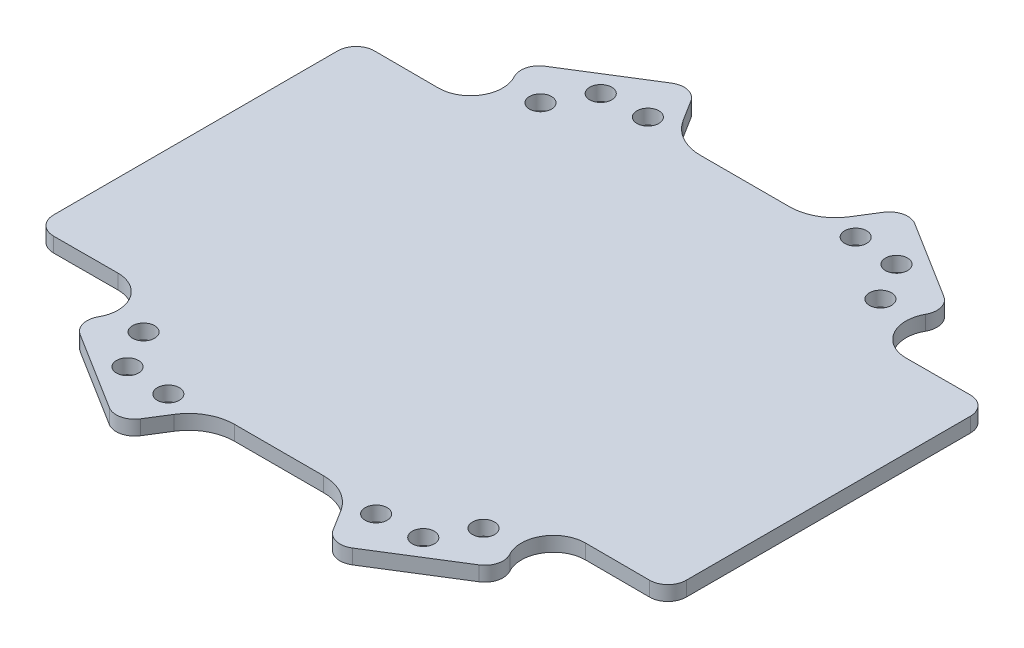
SolidWorks part; units mm, degrees
ref_plane "Front Plane" through (0, 0, 0) normal (0, 0, 1) x (1, 0, 0)
ref_plane "Top Plane" through (0, 0, 0) normal (0, 1, 0) x (1, 0, 0)
ref_plane "Right Plane" through (0, 0, 0) normal (1, 0, 0) x (0, 0, -1)
sketch "Sketch1" plane through (0, 0, 0) normal (0, 1, 0) x (1, 0, 0)
  line L0 (-17.5, 28) -> (-26.4999, 42.3999) construction
  line L1 (-28, 17.5) -> (28, 17.5) construction
  line L2 (-28, 17.5) -> (-28, -17.5) construction
  line L3 (-28, -17.5) -> (28, -17.5) construction
  line L4 (28, 17.5) -> (28, -17.5) construction
  line L5 (-28, 17.5) -> (28, -17.5) construction
  line L6 (-28, -17.5) -> (28, 17.5) construction
  line L7 (-17.5, 28) -> (17.5, 28) construction
  line L8 (-17.5, 28) -> (-17.5, -28) construction
  line L9 (-17.5, -28) -> (17.5, -28) construction
  line L10 (17.5, 28) -> (17.5, -28) construction
  line L11 (-17.5, 28) -> (17.5, -28) construction
  line L12 (-17.5, -28) -> (17.5, 28) construction
  line L13 (17.5, -28) -> (26.4999, -42.3999) construction
  line L14 (-23.436, 24.29) -> (-32.4359, 38.6899) construction
  line L15 (-23.436, 24.29) -> (11.564, -31.71) construction
  line L16 (11.564, -31.71) -> (20.564, -46.1099) construction
  line L17 (-11.564, 31.71) -> (-20.564, 46.1099) construction
  line L18 (-11.564, 31.71) -> (23.436, -24.29) construction
  line L19 (23.436, -24.29) -> (32.4359, -38.6899) construction
  line L20 (0, -28) -> (0, 28) construction
  line L21 (-34.5, 17.5) -> (-34.5, -17.5) construction
  line L22 (-34.5, 0) -> (34.5, 0) construction
  line L24 (34.5, 17.5) -> (34.5, -17.5) construction
  circle A0 centre (-26.4999, 42.3999) radius 25.4 construction
  circle A1 centre (-20, 9.5) radius 8 construction
  circle A2 centre (-26.4999, 42.3999) radius 8 construction
  point P4 (0, 0)
  point P11 (0, 0)
  dimension "D4" = 50.8
  dimension "D7" = 16
  dimension "D10" = 16
  dimension "D1" = 35
  dimension "D2" = 56
  dimension "D3" = 50
  dimension "D8" = 8
  dimension "D9" = 8
  dimension "D11" = 6.5
  dimension "D5" = 7
  dimension "D6" = 7
  dimension "D12" = 6.5
sketch "Sketch2" plane through (0, 0, 0) normal (0, 1, 0) x (1, 0, 0)
  line L0 (-34.5, -17.5) -> (-34.5, 17.5)
  line L1 (-34.5, 17.5) -> (-19.1649, 17.4563)
  line L2 (-23.436, 24.29) -> (11.564, -31.71) construction
  line L3 (-19.1649, 17.4563) -> (-23.436, 24.29)
  line L4 (-23.436, 24.29) -> (-11.564, 31.71)
  line L5 (-11.564, 31.71) -> (-7.6233, 25.4049)
  line L6 (-11.564, 31.71) -> (23.436, -24.29) construction
  line L7 (-7.6233, 25.4049) -> (7.6233, 25.4049)
  line L8 (0, -28) -> (0, 28) construction
  line L9 (0, -28) -> (0, 28) construction
  line L10 (-34.5, 0) -> (34.5, 0) construction
  line L11 (34.5, 17.5) -> (34.5, -17.5) construction
  line L12 (34.5, -17.5) -> (34.5, 17.5)
  line L13 (11.564, 31.71) -> (7.6233, 25.4049)
  line L14 (23.436, 24.29) -> (11.564, 31.71)
  line L15 (19.1649, 17.4563) -> (23.436, 24.29)
  line L16 (34.5, 17.5) -> (19.1649, 17.4563)
  line L17 (34.5, -17.5) -> (19.1649, -17.4563)
  line L18 (19.1649, -17.4563) -> (23.436, -24.29)
  line L19 (23.436, -24.29) -> (11.564, -31.71)
  line L20 (11.564, -31.71) -> (7.6233, -25.4049)
  line L21 (-7.6233, -25.4049) -> (7.6233, -25.4049)
  line L22 (-11.564, -31.71) -> (-7.6233, -25.4049)
  line L23 (-23.436, -24.29) -> (-11.564, -31.71)
  line L24 (-19.1649, -17.4563) -> (-23.436, -24.29)
  line L25 (-34.5, -17.5) -> (-19.1649, -17.4563)
  circle A0 centre (-20, 9.5) radius 8 construction
  circle A1 centre (-26.4999, 42.3999) radius 25.4 construction
  point P29 (0, 25.4049)
  point P43 (0, -25.4049)
extrude "Boss-Extrude1" add sketch "Sketch2" along normal mid plane 1.6
fillet "Fillet1" radius 3.5 4 edges at (19.1649, 0, 17.4563) (-19.1649, 0, 17.4563) (19.1649, 0, -17.4563) (-19.1649, 0, -17.4563)
fillet "Fillet2" radius 5 4 edges at (7.6233, 0, 25.4049) (-7.6233, 0, 25.4049) (7.6233, 0, -25.4049) (-7.6233, 0, -25.4049)
fillet "Fillet3" radius 2 12 edges at (34.5, 0, -17.5) (23.436, 0, -24.29) (34.5, 0, 17.5) (23.436, 0, 24.29) (11.564, 0, 31.71) (11.564, 0, -31.71) (-11.564, 0, -31.71) (-23.436, 0, -24.29) (-34.5, 0, -17.5) (-34.5, 0, 17.5) (-11.564, 0, 31.71) (-23.436, 0, 24.29)
sketch "Sketch3" plane through (0, 0.8, 0) normal (0, 1, 0) x (1, 0, 0)
  line L0 (-19.4953, 17.9849) -> (-7.6233, 25.4049) construction
  line L1 (-23.436, 24.29) -> (11.564, -31.71) construction
  line L2 (-11.564, 31.71) -> (23.436, -24.29) construction
  line L3 (-18.5386, 21.6429) -> (-16.1271, 25.8034) construction
  line L4 (-17.5, 28) -> (17.5, -28) construction
  line L5 (-18.5386, 21.6429) -> (-11.3306, 26.1479) construction
  line L6 (-11.3306, 26.1479) -> (-16.1271, 25.8034) construction
  circle A0 centre (-26.4999, 42.3999) radius 25.4 construction
  circle A1 centre (-16.1271, 25.8034) radius 1.2
  circle A2 centre (-11.3306, 26.1479) radius 1.2
  circle A3 centre (-18.5386, 21.6429) radius 1.2
  circle A4 centre (-18.5386, 21.6429) radius 1.9 construction
  circle A5 centre (-16.1271, 25.8034) radius 1.9 construction
  circle A6 centre (-11.3306, 26.1479) radius 1.9 construction
  point P12 (-14.9346, 23.8954)
  dimension "D2" = 2.4
  dimension "D5" = 3.8
  dimension "D1" = 4.25
  dimension "D3" = 2.25
  dimension "D4" = 2.595
extrude "Cut-Extrude1" cut sketch "Sketch3" against normal through all
mirror "Mirror1" about plane through (0, 0, 0) normal (1, 0, 0) of "Cut-Extrude1"
mirror "Mirror2" about plane through (0, 0, 0) normal (0, 0, 1) of "Cut-Extrude1", "Mirror1"
sketch "Sketch4" plane through (0, 0.8, 0) normal (0, 1, 0) x (1, 0, 0)
  circle A0 centre (-18.5386, 21.6429) radius 2.2 construction
  circle A1 centre (-16.1271, 25.8034) radius 2.2 construction
  circle A2 centre (-11.3306, 26.1479) radius 2.2 construction
  dimension "D1" = 4.4
equation "\"D4@Sketch3\"=(7.44-\"D3@Sketch3\")/2"
